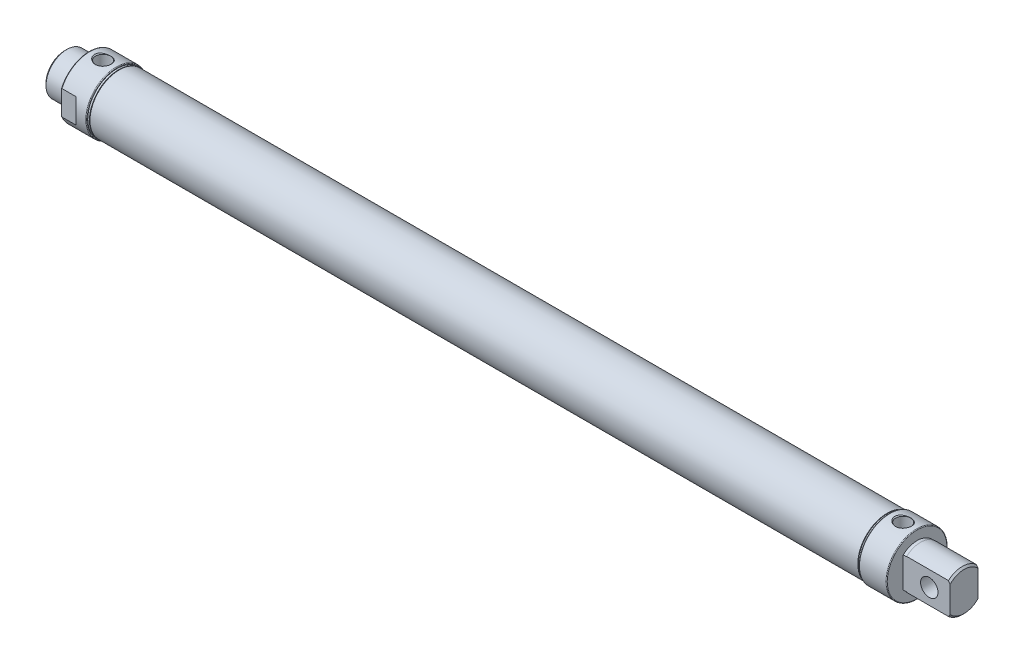
SolidWorks part; units mm, degrees
ref_plane "前视基准面" through (0, 0, 0) normal (0, 0, 1) x (1, 0, 0)
ref_plane "上视基准面" through (0, 0, 0) normal (0, 1, 0) x (1, 0, 0)
ref_plane "右视基准面" through (0, 0, 0) normal (1, 0, 0) x (0, 0, -1)
sketch "草图1" plane through (0, 0, 0) normal (0, 0, 1) x (1, 0, 0)
  line L0 (0, 0) -> (0, 10.773)
  line L1 (0, 10.773) -> (1.227, 12)
  line L2 (1.227, 12) -> (14, 12)
  line L3 (14, 12) -> (14, 17.1)
  line L4 (14.4, 17.5) -> (29.6, 17.5)
  line L5 (30, 17.1) -> (30, 16.8)
  line L6 (30, 16.8) -> (31, 16.8)
  line L7 (31, 16.8) -> (31, 16.3)
  line L8 (31, 16.3) -> (31.3, 16.8)
  line L9 (31.3, 16.8) -> (472.7, 16.8)
  line L10 (472.7, 16.8) -> (473, 16.3)
  line L11 (473, 16.3) -> (473, 16.8)
  line L12 (473, 16.8) -> (474, 16.8)
  line L13 (474, 16.8) -> (474, 17.1)
  line L14 (474.4, 17.5) -> (489.6, 17.5)
  line L15 (490, 17.1) -> (490, 0)
  line L16 (490, 0) -> (0, 0)
  line L17 (490, 0) -> (0, 0) construction
  arc A0 (14, 17.1) -> (14.4, 17.5) centre (14.4, 17.1) cw
  arc A1 (29.6, 17.5) -> (30, 17.1) centre (29.6, 17.1) cw
  arc A2 (474, 17.1) -> (474.4, 17.5) centre (474.4, 17.1) cw
  arc A3 (489.6, 17.5) -> (490, 17.1) centre (489.6, 17.1) cw
revolve "旋转1" add sketch "草图1" angle 360 about L17 reverse direction yes
cosmetic thread "装饰螺纹线1" parameters "D1"=12, "D2"=21.546
sketch "草图2" plane through (0, 0, 0) normal (0, 0, 1) x (1, 0, 0)
  line L0 (490, 0) -> (490, 11.85)
  line L1 (490, 11.85) -> (492, 11.85)
  line L2 (492, 11.85) -> (492, 12)
  line L3 (492, 12) -> (516, 12)
  line L4 (516, 12) -> (517, 11)
  line L5 (517, 11) -> (517, 0)
  line L6 (517, 0) -> (490, 0)
  line L7 (517, 0) -> (490, 0) construction
revolve "旋转2" add sketch "草图2" angle 360 about L7 reverse direction yes
cosmetic thread "装饰螺纹线2" parameters "D1"=25, "D2"=20.319
ref_plane "基准面4" through (14, 0, 0) normal (1, 0, 0) x (0, 0, -1)
ref_plane "基准面5" through (517, 0, 0) normal (1, 0, 0) x (0, 0, -1)
sketch "草图3" plane through (517, 0, 0) normal (1, 0, 0) x (0, 0, -1)
  line L0 (-18, 22) -> (-18, -22)
  line L1 (-18, -22) -> (18, -22)
  line L2 (18, -22) -> (18, 22)
  line L3 (18, 22) -> (-18, 22)
  line L4 (-8, 12) -> (-8, -12)
  line L5 (-8, -12) -> (8, -12)
  line L6 (8, -12) -> (8, 12)
  line L7 (8, 12) -> (-8, 12)
extrude "切除-拉伸1" cut sketch "草图3" against normal blind 27
ref_plane "基准面6" through (505, 0, 0) normal (1, 0, 0) x (0, 0, -1)
sketch "草图4" plane through (505, 0, 0) normal (1, 0, 0) x (0, 0, -1)
  line L0 (-8, 0) -> (-8, 5)
  line L1 (-8, 5) -> (8, 5)
  line L2 (8, 5) -> (8, 0)
  line L3 (8, 0) -> (-8, 0)
  line L4 (8, 0) -> (-8, 0) construction
revolve "切除-旋转1" cut sketch "草图4" angle 360 about L4 reverse direction yes
sketch "草图5" plane through (0, 0, 0) normal (0, 0, 1) x (1, 0, 0)
  line L0 (22, 17.5) -> (26.864, 17.5)
  line L1 (26.864, 17.5) -> (26.283, 16.919)
  line L2 (26.283, 16.919) -> (26.283, 9.5)
  line L3 (26.283, 9.5) -> (22, 9.5)
  line L4 (22, 9.5) -> (22, 17.5)
  line L5 (22, 9.5) -> (22, 17.5) construction
revolve "切除-旋转2" cut sketch "草图5" angle 360 about L5 reverse direction yes
cosmetic thread "装饰螺纹线3" parameters "D1"=8, "D2"=9.728
sketch "草图6" plane through (0, 0, 0) normal (0, 0, 1) x (1, 0, 0)
  line L0 (482, 17.5) -> (486.864, 17.5)
  line L1 (486.864, 17.5) -> (486.283, 16.919)
  line L2 (486.283, 16.919) -> (486.283, 9.5)
  line L3 (486.283, 9.5) -> (482, 9.5)
  line L4 (482, 9.5) -> (482, 17.5)
  line L5 (482, 9.5) -> (482, 17.5) construction
revolve "切除-旋转3" cut sketch "草图6" angle 360 about L5 reverse direction yes
cosmetic thread "装饰螺纹线4" parameters "D1"=8, "D2"=9.728
sketch "草图7" plane through (0, 0, 0) normal (0, 1, 0) x (1, 0, 0)
  line L0 (-4, -17.5) -> (24, -17.5)
  line L1 (24, -17.5) -> (22.5, -16)
  line L2 (22.5, -16) -> (-2, -16)
  line L3 (-2, -16) -> (-2, 16)
  line L4 (-2, 16) -> (22.5, 16)
  line L5 (22.5, 16) -> (24, 17.5)
  line L6 (24, 17.5) -> (-4, 17.5)
  line L7 (-4, 17.5) -> (-4, -17.5)
extrude "切除-拉伸2" cut sketch "草图7" along normal blind 35 and the other way blind 35
sketch "草图8" plane through (0, 0, 0) normal (0, 0, 1) x (1, 0, 0)
  line L0 (0, 0) -> (0, 6)
  line L1 (0, 6) -> (41, 6)
  line L2 (41, 6) -> (41, 16)
  line L3 (41, 16) -> (463, 16)
  line L4 (463, 16) -> (463, 0)
  line L5 (463, 0) -> (0, 0)
  line L6 (463, 0) -> (0, 0) construction
revolve "切除-旋转4" cut sketch "草图8" angle 360 about L6 reverse direction yes
ref_plane "基准面7" through (22, 0, 0) normal (1, 0, 0) x (0, 0, -1)
ref_plane "基准面8" through (0, 20.8, 0) normal (0, 1, 0) x (1, 0, 0)
ref_plane "基准面9" through (482, 0, 0) normal (1, 0, 0) x (0, 0, -1)
ref_plane "基准面10" through (6, 0, 0) normal (1, 0, 0) x (0, 0, -1)
ref_plane "基准面11" through (30, 0, 0) normal (1, 0, 0) x (0, 0, -1)
ref_plane "基准面12" through (14, 0, 0) normal (1, 0, 0) x (0, 0, -1)
ref_plane "基准面13" through (490, 0, 0) normal (1, 0, 0) x (0, 0, -1)
ref_plane "基准面14" through (498, 0, 0) normal (1, 0, 0) x (0, 0, -1)
ref_plane "基准面15" through (31, 0, 0) normal (1, 0, 0) x (0, 0, -1)
ref_plane "基准面16" through (473, 0, 0) normal (1, 0, 0) x (0, 0, -1)
ref_plane "IP_SWITCH1 XY" through (31, 0, 0) normal (-1, 0, 0) x (0, 0, 1)
ref_plane "IP_SWITCH1 XZ" through (0, 0, 0) normal (0, 1, 0) x (1, 0, 0)
ref_plane "IP_SWITCH1 YZ" through (0, 0, 0) normal (0, 0, -1) x (-1, 0, 0)
ref_axis "IP_SWITCH1 X" through (31, 0, 80.9) along (0, 0, -1)
ref_axis "IP_SWITCH1 Y" through (31, 50, 0) along (0, -1, 0)
ref_axis "IP_SWITCH1 Z" through (-80.9, 0, 0) along (1, 0, 0)
sketch3d "IP_SWITCH1"
  point P0 (31, 0, 0)
ref_plane "IP_SWITCH2 XY" through (473, 0, 0) normal (1, 0, 0) x (0, 0, -1)
ref_plane "IP_SWITCH2 XZ" through (0, 0, 0) normal (0, -1, 0) x (-1, 0, 0)
ref_plane "IP_SWITCH2 YZ" through (0, 0, 0) normal (0, 0, -1) x (-1, 0, 0)
ref_axis "IP_SWITCH2 X" through (473, 0, 80.9) along (0, 0, -1)
ref_axis "IP_SWITCH2 Y" through (473, -50, 0) along (0, 1, 0)
ref_axis "IP_SWITCH2 Z" through (80.9, 0, 0) along (-1, 0, 0)
sketch3d "IP_SWITCH2"
  point P0 (473, 0, 0)
ref_plane "body-dummy XY" through (30, 0, 0) normal (1, 0, 0) x (0, 0, -1)
ref_plane "body-dummy XZ" through (0, 0, 0) normal (0, -1, 0) x (-1, 0, 0)
ref_plane "body-dummy YZ" through (0, 0, 0) normal (0, 0, -1) x (-1, 0, 0)
ref_axis "body-dummy X" through (30, 0, 80.9) along (0, 0, -1)
ref_axis "body-dummy Y" through (30, -50, 0) along (0, 1, 0)
ref_axis "body-dummy Z" through (80.9, 0, 0) along (-1, 0, 0)
sketch3d "body-dummy"
  point P0 (30, 0, 0)
ref_plane "body-sdb XY" through (0, 0, 0) normal (0, 0, 1) x (1, 0, 0)
ref_plane "body-sdb XZ" through (0, 0, 0) normal (0, -1, 0) x (-1, 0, 0)
ref_plane "body-sdb YZ" through (505, 0, 0) normal (1, 0, 0) x (0, 0, -1)
ref_axis "body-sdb X" through (-80.9, 0, 0) along (1, 0, 0)
ref_axis "body-sdb Y" through (505, -50, 0) along (0, 1, 0)
ref_axis "body-sdb Z" through (505, 0, 80.9) along (0, 0, -1)
sketch3d "body-sdb"
  point P0 (505, 0, 0)
ref_plane "fa-body XY" through (14, 0, 0) normal (-1, 0, 0) x (0, 0, 1)
ref_plane "fa-body XZ" through (0, 0, 0) normal (0, 1, 0) x (1, 0, 0)
ref_plane "fa-body YZ" through (0, 0, 0) normal (0, 0, -1) x (-1, 0, 0)
ref_axis "fa-body X" through (14, 0, 80.9) along (0, 0, -1)
ref_axis "fa-body Y" through (14, 50, 0) along (0, -1, 0)
ref_axis "fa-body Z" through (-80.9, 0, 0) along (1, 0, 0)
sketch3d "fa-body"
  point P0 (14, 0, 0)
ref_plane "lb-body XY" through (490, 0, 0) normal (1, 0, 0) x (0, 0, -1)
ref_plane "lb-body XZ" through (0, 0, 0) normal (0, -1, 0) x (-1, 0, 0)
ref_plane "lb-body YZ" through (0, 0, 0) normal (0, 0, -1) x (-1, 0, 0)
ref_axis "lb-body X" through (490, 0, 80.9) along (0, 0, -1)
ref_axis "lb-body Y" through (490, -50, 0) along (0, 1, 0)
ref_axis "lb-body Z" through (80.9, 0, 0) along (-1, 0, 0)
sketch3d "lb-body"
  point P0 (490, 0, 0)
ref_plane "nut1-body XY" through (498, 0, 0) normal (1, 0, 0) x (0, 0, -1)
ref_plane "nut1-body XZ" through (0, 0, 0) normal (0, -1, 0) x (-1, 0, 0)
ref_plane "nut1-body YZ" through (0, 0, 0) normal (0, 0, -1) x (-1, 0, 0)
ref_axis "nut1-body X" through (498, 0, 80.9) along (0, 0, -1)
ref_axis "nut1-body Y" through (498, -50, 0) along (0, 1, 0)
ref_axis "nut1-body Z" through (80.9, 0, 0) along (-1, 0, 0)
sketch3d "nut1-body"
  point P0 (498, 0, 0)
ref_plane "nut2-body XY" through (6, 0, 0) normal (-1, 0, 0) x (0, 0, 1)
ref_plane "nut2-body XZ" through (0, 0, 0) normal (0, 1, 0) x (1, 0, 0)
ref_plane "nut2-body YZ" through (0, 0, 0) normal (0, 0, -1) x (-1, 0, 0)
ref_axis "nut2-body X" through (6, 0, 80.9) along (0, 0, -1)
ref_axis "nut2-body Y" through (6, 50, 0) along (0, -1, 0)
ref_axis "nut2-body Z" through (-80.9, 0, 0) along (1, 0, 0)
sketch3d "nut2-body"
  point P0 (6, 0, 0)
ref_plane "rod-body XY" through (0, 0, 0) normal (-1, 0, 0) x (0, 0, 1)
ref_plane "rod-body XZ" through (0, 0, 0) normal (0, 1, 0) x (1, 0, 0)
ref_plane "rod-body YZ" through (0, 0, 0) normal (0, 0, -1) x (-1, 0, 0)
ref_axis "rod-body X" through (0, 0, 80.9) along (0, 0, -1)
ref_axis "rod-body Y" through (0, 50, 0) along (0, -1, 0)
ref_axis "rod-body Z" through (-80.9, 0, 0) along (1, 0, 0)
sketch3d "rod-body"
  point P0 (0, 0, 0)
ref_plane "rod-nut XY" through (0, 0, 0) normal (-1, 0, 0) x (0, 0, 1)
ref_plane "rod-nut XZ" through (0, 0, 0) normal (0, 1, 0) x (1, 0, 0)
ref_plane "rod-nut YZ" through (0, 0, 0) normal (0, 0, -1) x (-1, 0, 0)
ref_axis "rod-nut X" through (0, 0, 80.9) along (0, 0, -1)
ref_axis "rod-nut Y" through (0, 50, 0) along (0, -1, 0)
ref_axis "rod-nut Z" through (-80.9, 0, 0) along (1, 0, 0)
sketch3d "rod-nut"
  point P0 (0, 0, 0)
